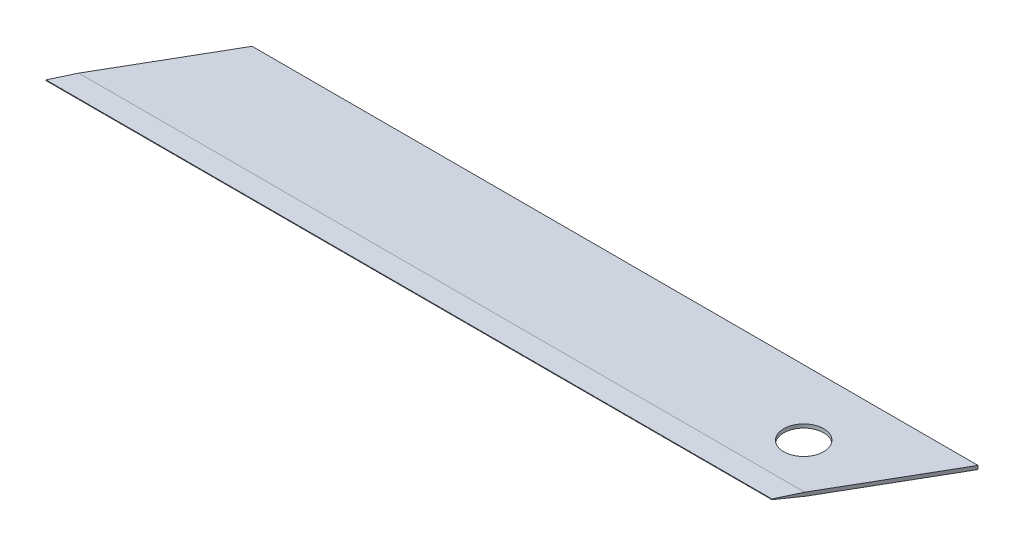
SolidWorks part; units mm, degrees
ref_plane "前视基准面" through (0, 0, 0) normal (0, 0, 1) x (1, 0, 0)
ref_plane "上视基准面" through (0, 0, 0) normal (0, 1, 0) x (1, 0, 0)
ref_plane "右视基准面" through (0, 0, 0) normal (1, 0, 0) x (0, 0, -1)
other "Configuration Table"
sketch "草图1" plane through (0, 0, 0) normal (0, 1, 0) x (1, 0, 0)
  line L0 (0, 0) -> (10.3923, 18)
  line L1 (0, 0) -> (100, 0)
  line L2 (10.3923, 18) -> (110.3923, 18)
  line L3 (100, 0) -> (110.3923, 18)
  dimension "D1" = 120
  dimension "D2" = 0
  dimension "D3" = 100
  dimension "D4" = 18
extrude "凸台-拉伸1" add sketch "草图1" along normal blind 0.5
sketch "草图2" plane through (0, 0, 0) normal (0, -1, 0) x (-1, 0, 0)
  line L0 (-110.3923, 18) -> (-10.3923, 18) construction
  line L1 (-100, 0) -> (-110.3923, 18) construction
  circle A0 centre (-95.3812, 9) radius 2.75
  dimension "D2" = 8.5
  dimension "D3" = 5.5
  dimension "D1" = 9
extrude "切除-拉伸1" cut sketch "草图2" against normal blind 10
chamfer "倒角1" distance 3 angle 4 1 edges at (50, 0, 0) first distance on face at (95.3812, 0, -11.75)
chamfer "倒角2" distance 0.2 angle 86 1 edges at (50, 0.5, 0) first distance on face at (50, 0.3549, 0)
